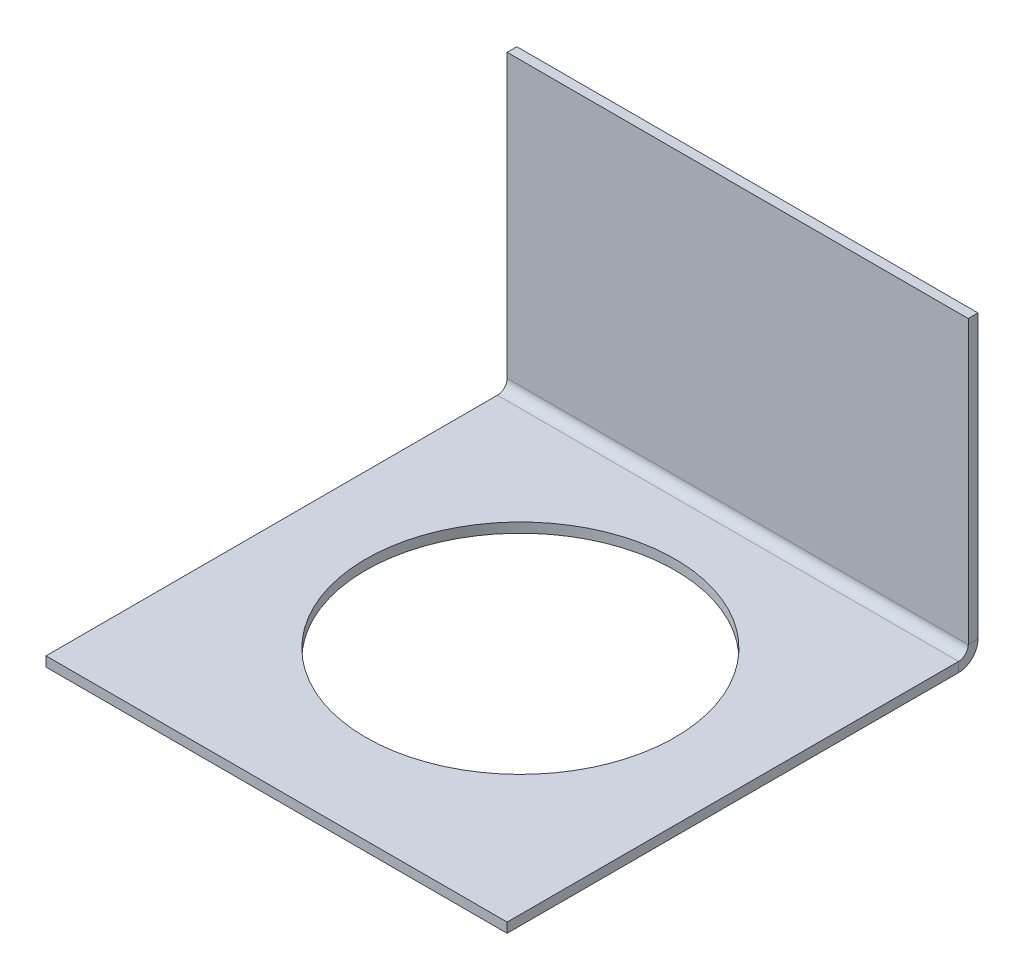
SolidWorks part; units mm, degrees
note: The reader was unsure of these and kept them because the rebuilt part matched: flange length of "Edge-Flange1".
ref_plane "Front Plane" through (0, 0, 0) normal (0, 0, 1) x (1, 0, 0)
ref_plane "Top Plane" through (0, 0, 0) normal (0, 1, 0) x (1, 0, 0)
ref_plane "Right Plane" through (0, 0, 0) normal (1, 0, 0) x (0, 0, -1)
sketch "Sketch10" plane through (0, 0, 0) normal (0, 1, 0) x (1, 0, 0)
  line L1 (0, 0) -> (47.36, 0)
  line L2 (0, 0) -> (0, -47.36)
  line L3 (0, -47.36) -> (47.36, -47.36)
  line L4 (47.36, 0) -> (47.36, -47.36)
  dimension "D1" = 47.36
  dimension "D2" = 47.36
base flange "Base-Flange1" sketch "Sketch10" thickness 1 reverse thickness direction no parameters "D1"=1
edge flange "Edge-Flange1" sketch "Sketch18" flange angle 90 flange length 30 flange position material outside bend radius 1 thickness 1 relief rectangular parameters "D6"=10
sketch "Sketch18" plane through (0, 0, 0) normal (0, 0, -1) x (-1, 0, 0)
  line L2 (-47.36, 0) -> (-47.36, 30)
  line L3 (-47.36, 30) -> (0, 30)
  line L4 (0, 30) -> (0, 0)
  line L5 (-47.36, 0) -> (0, 0) construction
  line L6 (-47.36, 0) -> (0, 0)
bend "EdgeBend1" bend radius 1 bend angle 90 parameters "D5"=1
sketch "Sketch20" plane through (0, 0, 0) normal (0, 1, 0) x (1, 0, 0)
  line L0 (0, 1) -> (47.36, 1) construction
  circle A0 centre (23.68, -22.32) radius 15.875
  point P2 (23.68, 1)
  dimension "D2" = 31.75
  dimension "D1" = 23.32
extrude "Cut-Extrude1" cut sketch "Sketch20" against normal through all normal cut yes
sketch "Bend-Lines1" [suppressed] plane through (0, 0, 0) normal (0, 1, 0) x (1, 0, 0)
sketch "Bounding-Box1" [suppressed] plane through (0, 0, 0) normal (0, 1, 0) x (1, 0, 0)
sketch "Sketch19" [suppressed] plane through (0, 0, 0) normal (0, 1, 0) x (1, 0, 0)
  line L0 (0, 30.3562) -> (47.36, 30.3562) construction
  circle A0 centre (23.68, -22.68) radius 15.875
  point P4 (23.68, 30.3562)
  dimension "D1" = 31.75
sheet metal parameters "Sheet-Metal(4)" thickness 1 parameters "D1"=1
flat pattern "Flat-Pattern(4)" [suppressed]
sketch "Bend-Lines2" plane through (0, 0, 0) normal (0, 1, 0) x (1, 0, 0)
sketch "Bounding-Box2" [suppressed] plane through (0, 0, 0) normal (0, 1, 0) x (1, 0, 0)
sheet metal parameters "Sheet-Metal(5)" thickness 1 parameters "D1"=1
flat pattern "Flat-Pattern(4)"
sketch "Bend-Lines2" plane through (0, 0, 0) normal (0, 1, 0) x (1, 0, 0)
  line L0 (47.36, 0.1781) -> (0, 0.1781) construction
  line L1 (47.36, 0.1781) -> (0, 0.1781) construction
sketch3d "Bounding-Box2" [suppressed]
  line L0 (0, 30.3562, 0) -> (0, -47.36, 0) construction
  line L1 (47.36, 30.3562, 0) -> (47.36, -47.36, 0) construction
  line L2 (0, 30.3562, 0) -> (47.36, 30.3562, 0) construction
  line L3 (0, -47.36, 0) -> (47.36, -47.36, 0) construction
bend of the flat pattern "Flatten-<EdgeBend1>1"
sheet metal parameters "Sheet-Metal(7)" thickness 1 parameters "D1"=1
flat pattern "Flat-Pattern(4)"
sketch "Bend-Lines2" plane through (0, 0, 0) normal (0, 1, 0) x (1, 0, 0)
  line L0 (47.36, 0.1781) -> (0, 0.1781) construction
  line L1 (47.36, 0.1781) -> (0, 0.1781) construction
sketch3d "Bounding-Box2" [suppressed]
  line L0 (0, 30.3562, 0) -> (0, -47.36, 0) construction
  line L1 (47.36, 30.3562, 0) -> (47.36, -47.36, 0) construction
  line L2 (0, 30.3562, 0) -> (47.36, 30.3562, 0) construction
  line L3 (0, -47.36, 0) -> (47.36, -47.36, 0) construction
bend of the flat pattern "Flatten-<EdgeBend1>1"
